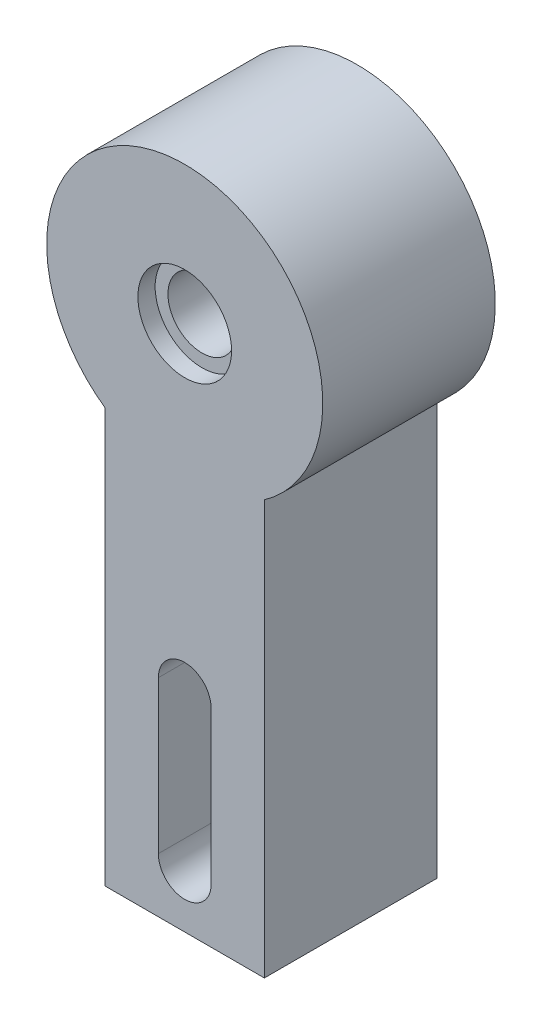
SolidWorks part; units mm, degrees
ref_plane "Piano frontale" through (0, 0, 0) normal (0, 0, 1) x (1, 0, 0)
ref_plane "Piano superiore" through (0, 0, 0) normal (0, 1, 0) x (1, 0, 0)
ref_plane "Piano destro" through (0, 0, 0) normal (1, 0, 0) x (0, 0, -1)
sketch "Schizzo1" plane through (0, 0, 0) normal (0, 0, 1) x (1, 0, 0)
  line L0 (0, 0) -> (0, 24)
  line L1 (0, 0) -> (9.2305, 0)
  line L2 (9.2305, 0) -> (9.2305, 24)
  line L6 (0, 12) -> (9.2305, 12) construction
  arc A0 (9.2305, 24) -> (0, 24) centre (4.6152, 30.5345) ccw
  point P16 (4.7974, 12)
  dimension "D1" = 24
  dimension "D3" = 16
  dimension "D2" = 24
  dimension "D4" = 9.2305
extrude "Estrusione-Estrusione1" add sketch "Schizzo1" along normal mid plane 10
sketch "Schizzo2" plane through (0, 0, 5) normal (0, 0, 1) x (1, 0, 0)
  line L0 (0, 12) -> (9.2305, 12) construction
  line L1 (0, 24) -> (0, 0) construction
  line L2 (9.2305, 0) -> (9.2305, 24) construction
  line L3 (4.6152, 12) -> (4.6152, 3.1687) construction
  line L4 (6.1457, 12) -> (6.1457, 3.1687)
  line L5 (3.0847, 12) -> (3.0847, 3.1687)
  line L6 (0, 0) -> (9.2305, 0) construction
  arc A0 (6.1457, 12) -> (3.0847, 12) centre (4.6152, 12) ccw
  arc A1 (3.0847, 3.1687) -> (6.1457, 3.1687) centre (4.6152, 3.1687) ccw
  point P8 (4.6152, 7.5843)
  dimension "D1" = 1.5305
  dimension "D2" = 3.1687
extrude "Taglio-Estrusione1" cut sketch "Schizzo2" against normal through all
sketch "Schizzo3" plane through (0, 0, 5) normal (0, 0, 1) x (1, 0, 0)
  circle A0 centre (4.6152, 30.5345) radius 2.7151
extrude "Taglio-Estrusione2" cut sketch "Schizzo3" against normal blind 1
sketch "Schizzo4" plane through (0, 0, 4) normal (0, 0, 1) x (1, 0, 0)
  circle A0 centre (4.6152, 30.5345) radius 1.9735
extrude "Taglio-Estrusione3" cut sketch "Schizzo4" against normal through all
